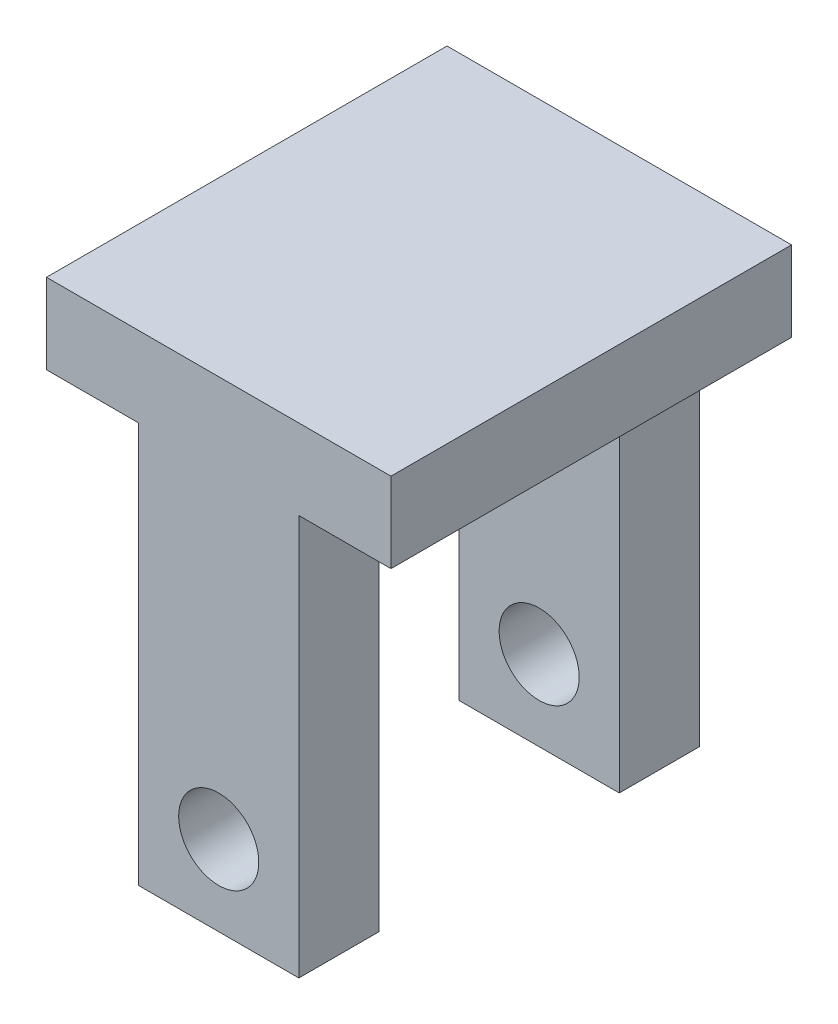
SolidWorks part; units mm, degrees
ref_plane "Plan de face" through (0, 0, 0) normal (0, 0, 1) x (1, 0, 0)
ref_plane "Plan de dessus" through (0, 0, 0) normal (0, 1, 0) x (1, 0, 0)
ref_plane "Plan de droite" through (0, 0, 0) normal (1, 0, 0) x (0, 0, -1)
sketch "Esquisse1" plane through (0, 0, 0) normal (0, 0, 1) x (1, 0, 0)
  line L0 (2, 0) -> (-2, 0)
  line L1 (2, 0) -> (2, 10)
  line L2 (2, 10) -> (4.3, 10)
  line L3 (4.3, 10) -> (4.3, 12)
  line L5 (-4.3, 12) -> (4.3, 12)
  line L6 (0, 12) -> (0, 0) construction
  line L7 (-4.3, 10) -> (-4.3, 12)
  line L8 (-2, 10) -> (-4.3, 10)
  line L9 (-2, 0) -> (-2, 10)
  dimension "D1" = 12
  dimension "D2" = 4.3
  dimension "D3" = 2
  dimension "D4" = 2
extrude "Boss.-Extru.1" add sketch "Esquisse1" along normal blind 10
sketch "Esquisse2" plane through (2, 0, 0) normal (1, 0, 0) x (0, 0, -1)
  line L0 (-10, 0) -> (0, 0) construction
  line L1 (-8, 0) -> (-2, 0)
  line L2 (-8, 0) -> (-8, 8)
  line L3 (-8, 8) -> (-2, 8)
  line L4 (-2, 0) -> (-2, 8)
  dimension "D1" = 2
  dimension "D2" = 2
  dimension "D3" = 8
extrude "Enlèv. mat.-Extru.1" cut sketch "Esquisse2" against normal through all
sketch "Esquisse3" plane through (0, 0, 0) normal (0, 0, -1) x (-1, 0, 0)
  line L0 (-4.3, 12) -> (4.3, 12) construction
  circle A0 centre (0, 2) radius 1
  dimension "D2" = 2
  dimension "D1" = 10
extrude "Enlèv. mat.-Extru.2" cut sketch "Esquisse3" against normal through all
